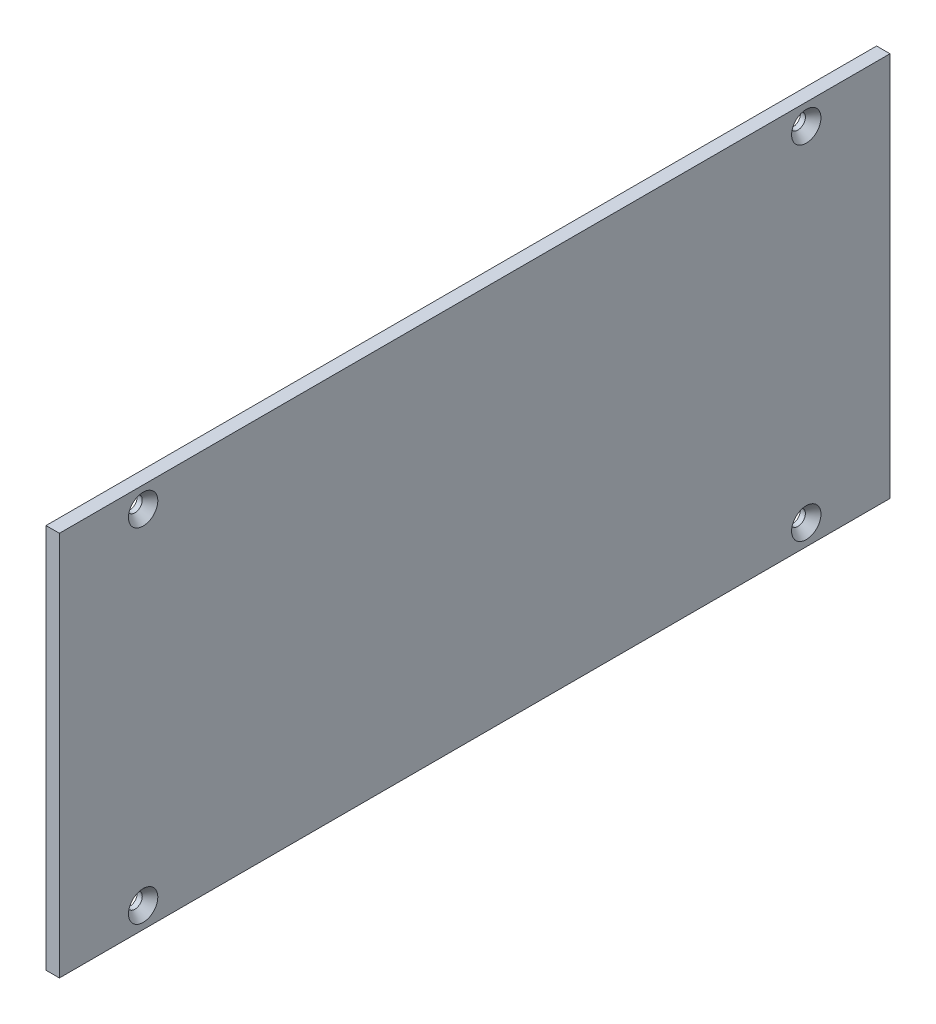
SolidWorks part; units mm, degrees
material "6061-T4 (SS)"
ref_plane "Front Plane" through (0, 0, 0) normal (0, 0, 1) x (1, 0, 0)
ref_plane "Top Plane" through (0, 0, 0) normal (0, 1, 0) x (1, 0, 0)
ref_plane "Right Plane" through (0, 0, 0) normal (1, 0, 0) x (0, 0, -1)
sketch "Sketch1" plane through (0, 0, 0) normal (1, 0, 0) x (0, 0, -1)
  line L1 (0, 0) -> (99.2004, 0)
  line L2 (0, 0) -> (0, 46)
  line L3 (0, 46) -> (99.2004, 46)
  line L4 (99.2004, 0) -> (99.2004, 46)
  dimension "D1" = 46
  dimension "D2" = 99.2004
extrude "Boss-Extrude1" add sketch "Sketch1" along normal blind 1.6002
hole_wizard "CSK for #0 Flat Head Socket Cap Screw1" positions "Sketch3" profile "Sketch4" countersink size "#0" standard "ANSI Inch" end condition through all
sketch "Sketch3" plane through (1.6002, 0, 0) normal (1, 0, 0) x (0, 0, -1)
  line L0 (10, 43.5) -> (10, 2.5) construction
  line L1 (10, 2.5) -> (89.2004, 2.5) construction
  line L2 (89.2004, 2.5) -> (89.2004, 43.5) construction
  line L3 (89.2004, 43.5) -> (10, 43.5) construction
  line L5 (0, 23) -> (10, 23) construction
  line L6 (0, 46) -> (0, 0) construction
  line L7 (10, 23) -> (89.2004, 23) construction
  line L8 (89.2004, 23) -> (99.2004, 23) construction
  line L9 (99.2004, 0) -> (99.2004, 46) construction
  line L11 (99.2004, 46) -> (0, 46) construction
  line L12 (0, 0) -> (99.2004, 0) construction
  point P0 (10, 43.5)
  point P2 (10, 2.5)
  point P4 (89.2004, 2.5)
  point P6 (89.2004, 43.5)
  dimension "D1" = 10
  dimension "D2" = 2.5
  dimension "D3" = 2.5
  dimension "D4" = 10
sketch "Sketch4" plane through (1.6002, 43.5, -10) normal (0, 1, 0) x (0, 0, -1)
  line L0 (0, 0) -> (0, 1.6002)
  line L1 (0, 1.6002) -> (0.889, 1.6002)
  line L2 (0.889, 1.6002) -> (0.889, 0.9935)
  line L3 (0.889, 0.9935) -> (1.7526, 0)
  line L5 (1.7526, 0) -> (0, 0)
  line L6 (-0.889, 0.9935) -> (-1.7526, 0) construction
  line L11 (0, -6.35) -> (0, 107.95) construction
  dimension "Thru Hole Dia." = 1.778
  dimension "Thru Hole Depth" = 1.6002
  dimension "Near C'Sink Dia." = 3.5052
  dimension "Near C'Sink Angle" = 82
